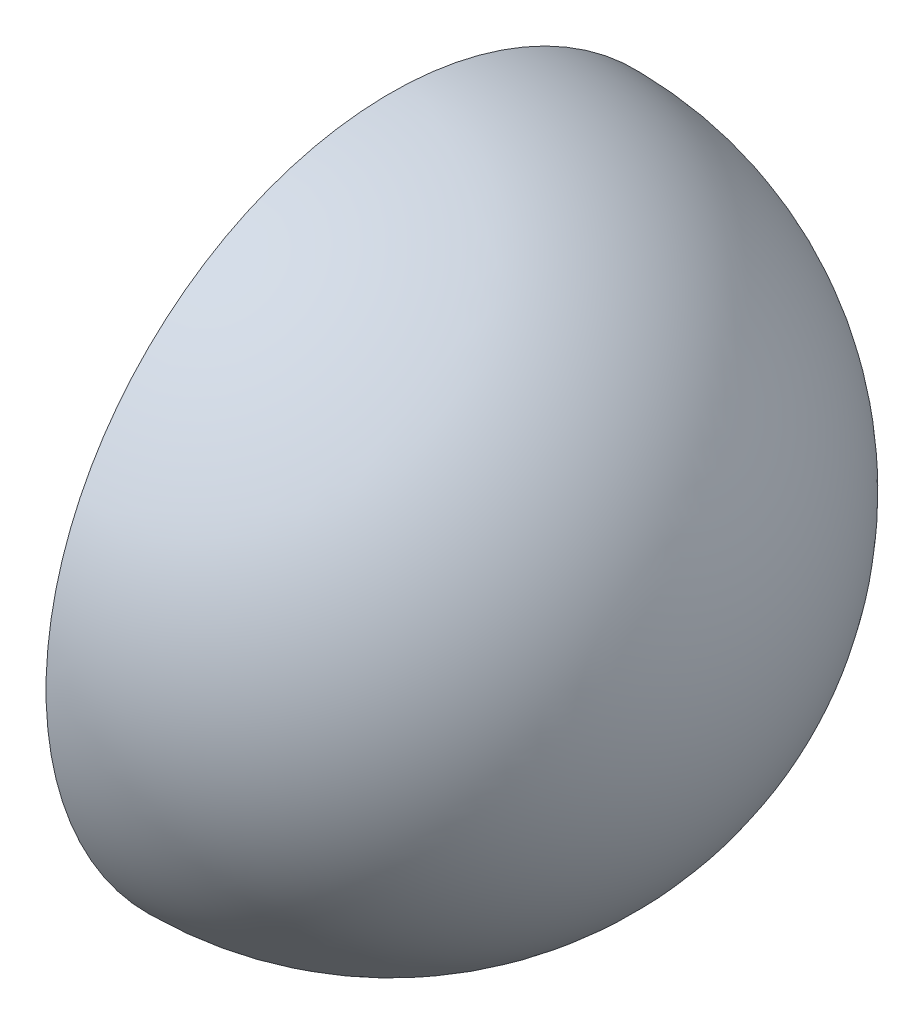
SolidWorks part; units mm, degrees
ref_plane "Front Plane" through (0, 0, 0) normal (0, 0, 1) x (1, 0, 0)
ref_plane "Top Plane" through (0, 0, 0) normal (0, 1, 0) x (1, 0, 0)
ref_plane "Right Plane" through (0, 0, 0) normal (1, 0, 0) x (0, 0, -1)
sketch "Sketch2" plane through (0, 0, 0) normal (1, 0, 0) x (0, 0, -1)
  circle A0 centre (0, 0) radius 25
extrude "Boss-Extrude1" add sketch "Sketch2" along normal blind 25
fillet "Fillet1" radius 25 1 edges at (25, 0, -25)
sketch "Sketch3" plane through (0, 0, 0) normal (-1, 0, 0) x (0, 0, 1)
  circle A0 centre (0, 0) radius 13
extrude "Cut-Extrude1" cut sketch "Sketch3" against normal blind 15
thread "Thread2" pitch 5 method extrude profile "Thread Profile3" start angle 5, offset 4, length 15, pitch 5, diameter 26
ref_plane "Plane3" through (-4, 1.133, -12.9505) normal (0, -0.9962, -0.0872) x (0, 0.0872, -0.9962)
sketch "Thread Profile3" plane through (-4, 1.133, -12.9505) normal (0, -0.9962, -0.0872) x (0, 0.0872, -0.9962)
  line L0 (0, 0) -> (0, 5) construction
  line L11 (0, 0) -> (0, 4.375)
  line L12 (0, 4.375) -> (-2.7063, 2.8125)
  line L13 (-2.7063, 2.8125) -> (-2.7063, 1.5625)
  line L15 (-2.7063, 1.5625) -> (0, 0)
  line L17 (-2.7063, 2.1875) -> (0, 2.1875) construction
  point P2 (0, 0)
  dimension "Pitch" = 5
  dimension "Profile_Angle" = 60
  dimension "Profile_Land" = 1.25
  dimension "Profile_Height" = 2.7063
sketch "Sketch17" plane through (0, 0, 0) normal (-1, 0, 0) x (0, 0, 1)
  line L1 (-15.6031, 15.2854) -> (16.6621, 15.2854)
  line L2 (-15.6031, 15.2854) -> (-15.6031, -15.8502)
  line L3 (-15.6031, -15.8502) -> (16.6621, -15.8502)
  line L4 (16.6621, 15.2854) -> (16.6621, -15.8502)
  point P4 (7.8368, -8.5782)
extrude "Cut-Extrude2" cut sketch "Sketch17" along normal blind 70
